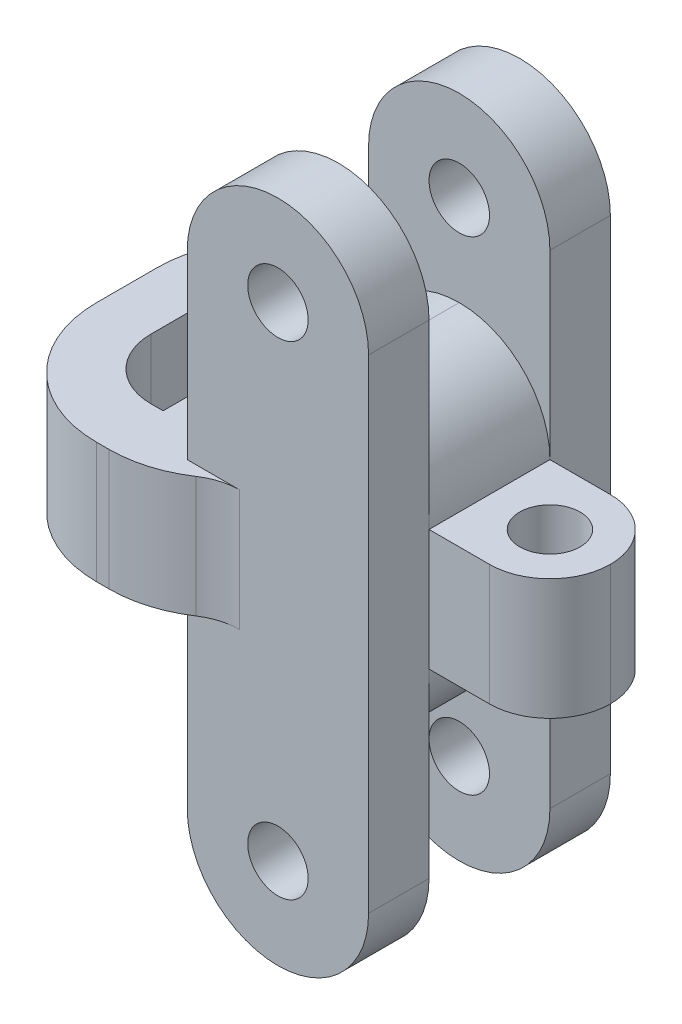
SolidWorks part; units mm, degrees
ref_plane "前视基准面" through (0, 0, 0) normal (0, 0, 1) x (1, 0, 0)
ref_plane "上视基准面" through (0, 0, 0) normal (0, 1, 0) x (1, 0, 0)
ref_plane "右视基准面" through (0, 0, 0) normal (1, 0, 0) x (0, 0, -1)
other "Configuration Table"
sketch "Sketch1" plane through (0, 0, 0) normal (0, 0, 1) x (1, 0, 0)
  line L1 (-7.5, -12.5) -> (7.5, -12.5)
  line L2 (-7.5, -12.5) -> (-7.5, 12.5)
  line L3 (-7.5, 12.5) -> (7.5, 12.5)
  line L4 (7.5, -12.5) -> (7.5, 12.5)
  line L5 (-7.5, -12.5) -> (7.5, 12.5) construction
  line L6 (-7.5, 12.5) -> (7.5, -12.5) construction
  point P0 (0, 0)
  dimension "D1" = 15
  dimension "D2" = 25
extrude "Boss-Extrude1" add sketch "Sketch1" along normal mid plane 10
sketch "Sketch2" plane through (0, 0, 5) normal (0, 0, 1) x (1, 0, 0)
  line L0 (0, -20) -> (0, 20) construction
  line L2 (-7.5, 20) -> (-7.5, -20)
  line L5 (-7.5, 0) -> (0, 0)
  line L6 (7.5, 20) -> (7.5, -20)
  circle A0 centre (0, 20) radius 2.5
  circle A1 centre (0, 20) radius 7.5
  circle A2 centre (0, -20) radius 7.5
  circle A3 centre (0, -20) radius 2.5
  dimension "D1" = 15
  dimension "D2" = 5
  dimension "D6" = 5
  dimension "D7" = 15
  dimension "D3" = 20
  dimension "D4" = 90
  dimension "D5" = 40
extrude "Boss-Extrude2" add sketch "Sketch2" along normal blind 5
mirror "Mirror1" about plane through (0, 0, 0) normal (0, 0, 1) of "Boss-Extrude2"
fillet "Fillet1" radius 7.5 4 edges at (7.5, -12.5, 0) (-7.5, -12.5, 0) (-7.5, 12.5, 0) (7.5, 12.5, 0)
sketch "Sketch3" plane through (7.5, 0, 0) normal (1, 0, 0) x (0, 0, -1)
  line L1 (-5, -5) -> (5, -5)
  line L2 (-5, -5) -> (-5, 5)
  line L3 (-5, 5) -> (5, 5)
  line L4 (5, -5) -> (5, 5)
  line L5 (-5, -5) -> (5, 5) construction
  line L6 (-5, 5) -> (5, -5) construction
  point P0 (0, 0)
extrude "Boss-Extrude3" add sketch "Sketch3" along normal blind 10
fillet "Fillet2" radius 5 2 edges at (17.5, 0, 5) (17.5, 0, -5)
sketch "Sketch4" plane through (0, 5, 0) normal (0, 1, 0) x (1, 0, 0)
  circle A0 centre (12.5, 0) radius 2.5
  dimension "D1" = 5
extrude "Cut-Extrude1" cut sketch "Sketch4" against normal blind 10
sketch "Sketch5" plane through (-7.5, 0, 0) normal (-1, 0, 0) x (0, 0, 1)
  line L1 (-12.5, -5) -> (12.5, -5)
  line L2 (-12.5, -5) -> (-12.5, 5)
  line L3 (-12.5, 5) -> (12.5, 5)
  line L4 (12.5, -5) -> (12.5, 5)
  line L5 (-12.5, -5) -> (12.5, 5) construction
  line L6 (-12.5, 5) -> (12.5, -5) construction
  point P0 (0, 0)
  dimension "D1" = 10
  dimension "D2" = 25
extrude "Boss-Extrude4" add sketch "Sketch5" along normal blind 15
sketch "Sketch6" plane through (0, -5, 0) normal (0, -1, 0) x (1, 0, 0)
  line L0 (-15, 12.5) -> (-15, -12.5) construction
  line L1 (-22.5, 12.5) -> (-7.5, 12.5) construction
  line L2 (-22.5, -12.5) -> (-7.5, -12.5) construction
  line L3 (-15, -12.5) -> (-15, 0) construction
  line L5 (-18, -7.5) -> (-12, -7.5)
  line L6 (-18, -7.5) -> (-18, 7.5)
  line L7 (-18, 7.5) -> (-12, 7.5)
  line L8 (-12, -7.5) -> (-12, 7.5)
  line L9 (-18, -7.5) -> (-12, 7.5) construction
  line L10 (-18, 7.5) -> (-12, -7.5) construction
  dimension "D1" = 6
  dimension "D2" = 15
extrude "Cut-Extrude2" cut sketch "Sketch6" against normal blind 15
fillet "Fillet3" radius 5 2 edges at (-7.5, 0, 10) (-7.5, 0, -10)
fillet "Fillet4" radius 10 4 edges at (-7.5, 0, 12.5) (-7.5, 0, -12.5) (-22.5, 0, 12.5) (-22.5, 0, -12.5)
fillet "Fillet5" radius 5 2 edges at (-18, 0, 7.5) (-18, 0, -7.5)
